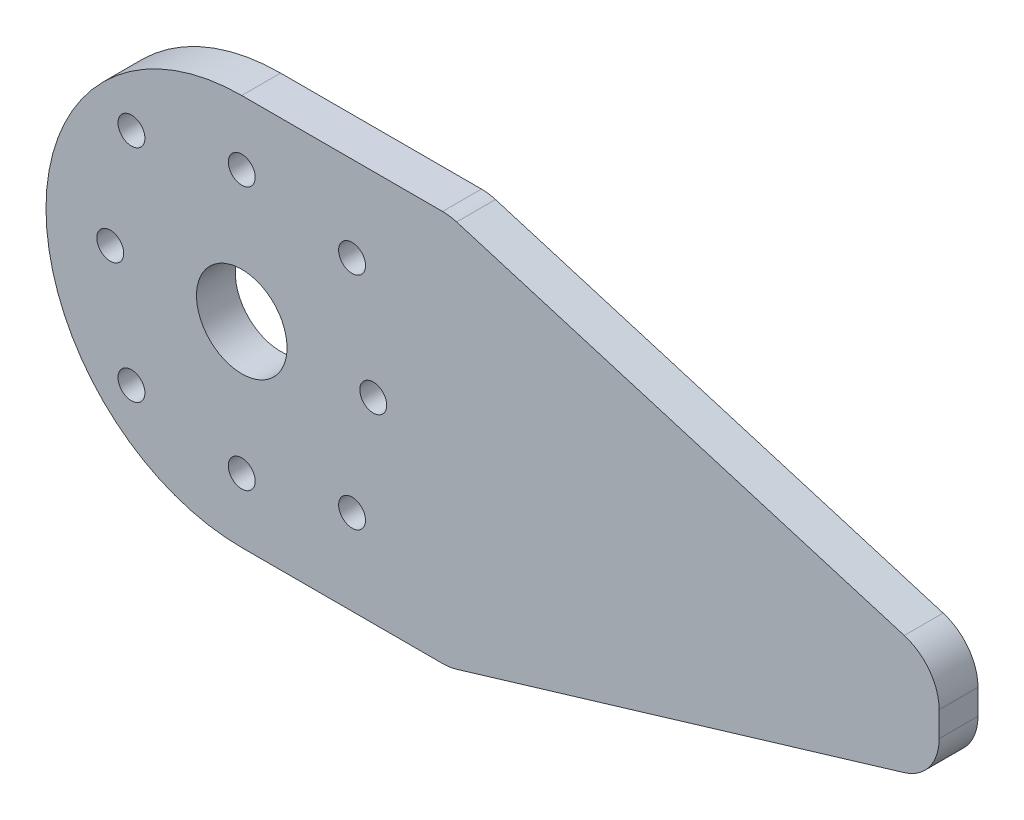
SolidWorks part; units mm, degrees
ref_plane "Front Plane" through (0, 0, 0) normal (0, 0, 1) x (1, 0, 0)
ref_plane "Top Plane" through (0, 0, 0) normal (0, 1, 0) x (1, 0, 0)
ref_plane "Right Plane" through (0, 0, 0) normal (1, 0, 0) x (0, 0, -1)
sketch "Sketch1" plane through (0, 0, 0) normal (0, 0, 1) x (1, 0, 0)
  line L1 (19, 0) -> (76, 0)
  line L3 (19, 32) -> (76, 32)
  line L4 (76, 0) -> (76, 32)
  arc A0 (19, 32) -> (19, 0) centre (19, 16) ccw
  circle A1 centre (8.25, 16) radius 1.1
  circle A2 centre (9.9844, 25.0156) radius 1.1
  circle A3 centre (28.0156, 25.0156) radius 1.1
  circle A4 centre (28.0156, 6.9844) radius 1.1
  circle A5 centre (9.9844, 6.9844) radius 1.1
  circle A6 centre (19, 26.75) radius 1.1
  circle A7 centre (29.75, 16) radius 1.1
  circle A8 centre (19, 5.25) radius 1.1
  circle A9 centre (19, 16) radius 3.7
  point P19 (19, 16)
  point P24 (19, 16)
  point P27 (19, 16)
  point P42 (19, 16)
  dimension "D3" = 19
  dimension "D6" = 10.75
  dimension "D7" = 7.4
  dimension "D8" = 2.2
  dimension "D10" = 4
  dimension "D5" = 12.75
  dimension "D4" = 2.2
  dimension "D1" = 32
  dimension "D2" = 57
  dimension "D9" = 45
  dimension "D11" = 4
extrude "Boss-Extrude1" add sketch "Sketch1" along normal blind 3.175
sketch "Sketch2" plane through (0, 0, 3.175) normal (0, 0, 1) x (1, 0, 0)
  line L0 (76, 32) -> (76, 20)
  line L1 (76, 0) -> (76, 32) construction
  line L2 (76, 20) -> (36, 32)
  line L3 (76, 32) -> (19, 32) construction
  line L4 (36, 32) -> (76, 32)
  line L5 (76, 0) -> (76, 12)
  line L6 (76, 12) -> (36, 0)
  line L7 (19, 0) -> (76, 0) construction
  line L8 (36, 0) -> (76, 0)
  dimension "D1" = 12
  dimension "D2" = 40
  dimension "D3" = 12
  dimension "D4" = 40
extrude "Cut-Extrude1" cut sketch "Sketch2" against normal blind 3.175
fillet "Fillet1" radius 4 4 edges at (36, 32, 1.5875) (36, 0, 1.5875) (76, 20, 1.5875) (76, 12, 1.5875)
